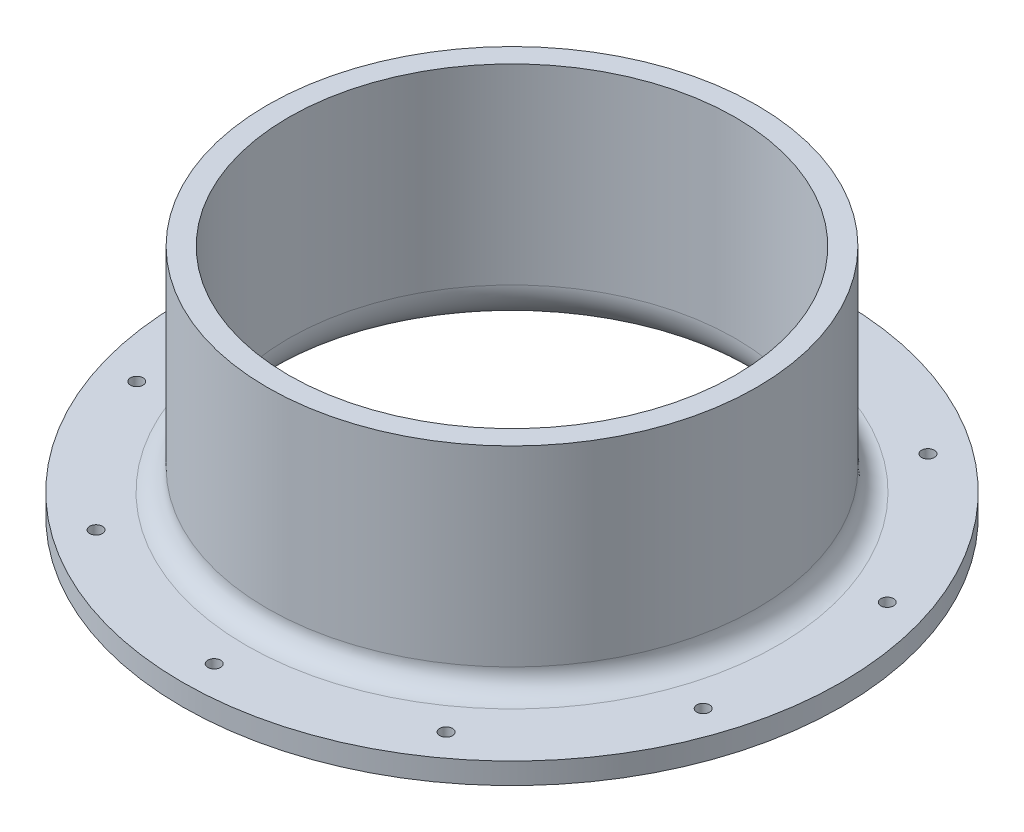
SolidWorks part; units mm, degrees
ref_plane "Front Plane" through (0, 0, 0) normal (0, 0, 1) x (1, 0, 0)
ref_plane "Top Plane" through (0, 0, 0) normal (0, 1, 0) x (1, 0, 0)
ref_plane "Right Plane" through (0, 0, 0) normal (1, 0, 0) x (0, 0, -1)
sketch "Sketch2" plane through (0, 0, 0) normal (0, 1, 0) x (1, 0, 0)
  line L0 (0, 0) -> (0, 88.9) construction
  line L5 (0, 88.9) -> (0, 98.425) construction
  circle A0 centre (0, 0) radius 73.025
  circle A9 centre (0, 0) radius 66.675
  circle A10 centre (0, 0) radius 98.425
  circle A11 centre (0, 88.9) radius 1.9
  point P6 (106.5634, 45.042)
  point P8 (0, 0)
  point P37 (0, 0)
  dimension "D1" = 146.05
  dimension "D4" = 3.8
  dimension "D9" = 6.35
  dimension "D2" = 25.4
  dimension "D3" = 9.525
extrude "Boss-Extrude1" add sketch "Sketch2" against normal blind 6.35 contours A10 A11 A0 | A11 | A0 A9 region at (-70.9595, 0, 0) region at (-95.6411, 0, 0) region at (0, 0, -88.9)
extrude "Boss-Extrude2" add sketch "Sketch2<3>" along normal blind 63.5 contours A0 A9 | A0 A9 region at (-70.9595, 0, 0)
sketch "Sketch2<3>" plane through (0, 0, 0) normal (0, 1, 0) x (1, 0, 0) same geometry as "Sketch2"
fillet "Fillet1" radius 6.35 1 edges at (0, 0, 73.025)
fillet "Fillet2" radius 12.7 1 edges at (0, -6.35, 66.675)
chamfer "Chamfer1" [suppressed] distance 3.175 angle 45
extrude "Cut-Extrude2" cut sketch "Sketch2<5>" against normal through all contours A11
sketch "Sketch2<5>" plane through (0, 0, 0) normal (0, 1, 0) x (1, 0, 0) same geometry as "Sketch2"
chamfer "Chamfer2" distance 1.524 angle 45 1 edges at (0, -6.35, -87)
ref_axis "Axis1" through (0, 0, 0) along (0, 1, 0)
pattern_circular "CirPattern1" count 10 over 360 about axis through (0, 0, 0) along (0, 1, 0) of "Cut-Extrude2", "Chamfer2"
